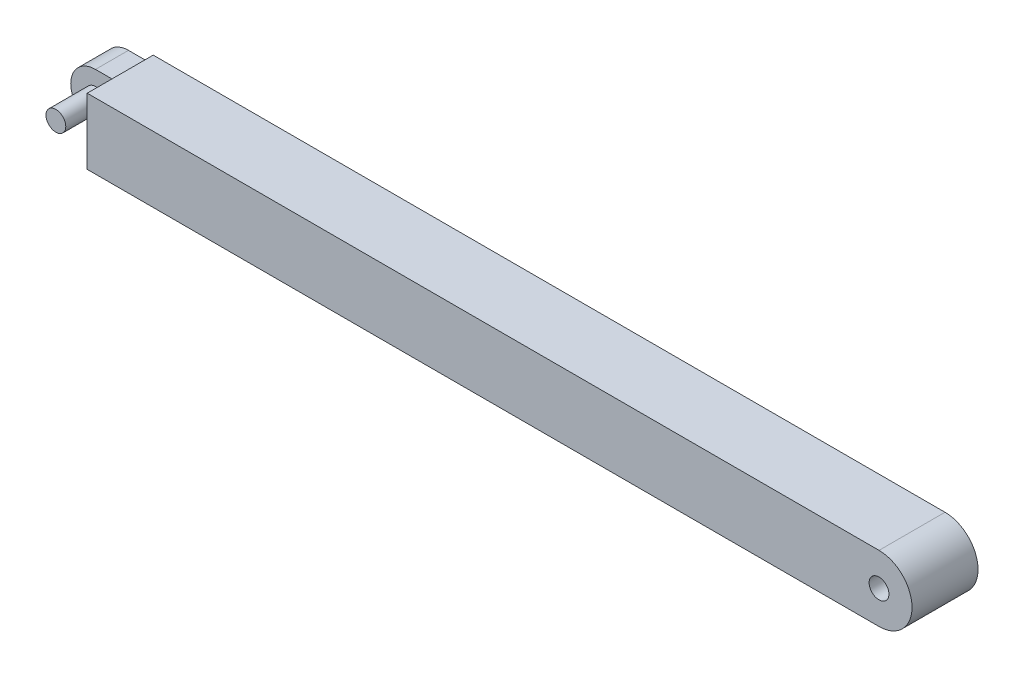
SolidWorks part; units mm, degrees
ref_plane "Front Plane" through (0, 0, 0) normal (0, 0, 1) x (1, 0, 0)
ref_plane "Top Plane" through (0, 0, 0) normal (0, 1, 0) x (1, 0, 0)
ref_plane "Right Plane" through (0, 0, 0) normal (1, 0, 0) x (0, 0, -1)
sketch "Sketch3" plane through (0, 0, 0) normal (0, 0, 1) x (1, 0, 0)
  line L1 (0, 0) -> (50.8, 0)
  line L2 (0, 0) -> (0, -4.2333)
  line L3 (0, -4.2333) -> (50.8, -4.2333)
  arc A0 (50.8, 0) -> (50.8, -4.2333) centre (50.8, -2.1167) cw
  dimension "D1" = 50.8
  dimension "D2" = 4.2333
extrude "Boss-Extrude3" add sketch "Sketch3" along normal blind 4.2333
sketch "Sketch4" plane through (0, 0, 0) normal (-1, 0, 0) x (0, 0, 1)
  line L0 (0, 0) -> (0, -4.2333) construction
  line L1 (0, -0.5292) -> (2.1167, -0.5292)
  line L2 (0, -0.5292) -> (0, -3.7042)
  line L3 (0, -3.7042) -> (2.1167, -3.7042)
  line L4 (2.1167, -0.5292) -> (2.1167, -3.7042)
  point P7 (0, -2.1167)
  point P8 (0, -2.1167)
  dimension "D1" = 0
  dimension "D2" = 2.1167
  dimension "D3" = 3.175
extrude "Boss-Extrude5" add sketch "Sketch4" along normal blind 3.175
sketch "Sketch5" plane through (0, 0, 0) normal (0, 0, -1) x (-1, 0, 0)
  line L0 (3.175, -0.5292) -> (0, -0.5292) construction
  line L1 (3.175, -3.7042) -> (0, -3.7042) construction
  arc A0 (1.5875, -0.5292) -> (1.5875, -3.7042) centre (1.5875, -2.1167) cw
  dimension "D1" = 1.5875
extrude "Cut-Extrude1" cut sketch "Sketch5" against normal blind 3.175 and the other way through all
ref_point "Point1"
sketch "Sketch6" plane through (0, 0, 2.1167) normal (0, 0, 1) x (1, 0, 0)
  circle A0 centre (-1.5875, -2.1167) radius 0.635
  dimension "D1" = 1.27
extrude "Boss-Extrude6" add sketch "Sketch6" along normal blind 2.54
ref_point "Point2"
ref_point "Point3"
sketch "Sketch7" plane through (0, 0, 4.2333) normal (0, 0, 1) x (1, 0, 0)
  circle A0 centre (50.8, -2.1167) radius 0.635
  dimension "D1" = 1.27
extrude "Cut-Extrude2" cut sketch "Sketch7" against normal blind 1.27
sketch "Sketch8" plane through (0, 0, 0) normal (0, 0, -1) x (-1, 0, 0)
  circle A0 centre (-50.8, -2.1167) radius 0.635
  dimension "D1" = 1.27
extrude "Cut-Extrude3" cut sketch "Sketch8" against normal blind 1.27
